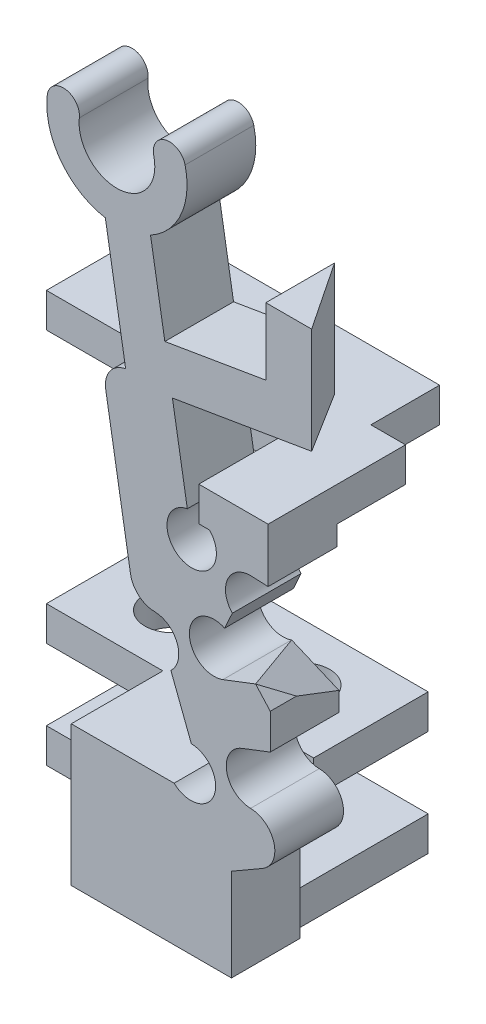
SolidWorks part; units mm, degrees
ref_plane "Front Plane" through (0, 0, 0) normal (0, 0, 1) x (1, 0, 0)
ref_plane "Top Plane" through (0, 0, 0) normal (0, 1, 0) x (1, 0, 0)
ref_plane "Right Plane" through (0, 0, 0) normal (1, 0, 0) x (0, 0, -1)
sketch "Sketch-SkeletonConfigUp" plane through (0, 0, 0) normal (0, 0, 1) x (1, 0, 0)
  line L0 (0, 0) -> (0, -50000) construction
  line L1 (0, 0) -> (4.5811, 6.2164) construction
  line L2 (9.8143, 13.3177) -> (4.5811, 13.945) construction
  line L3 (4.5811, 13.945) -> (2.9713, 10.4094) construction
  line L4 (2.9713, 10.4094) -> (4.5811, 6.2164) construction
  line L5 (4.5811, 13.945) -> (6.2429, 19.1409) construction
  line L6 (2.9713, 10.4094) -> (0.0405, 27.8193) construction
  line L7 (4.5811, 6.2164) -> (9.8143, 13.3177) construction
  line L8 (-587.3593, -797.0242) -> (9.8143, 13.3177) construction
  dimension "D2" = 7.7221
  dimension "D3" = 8.8212
  dimension "D4" = 5.2707
  dimension "D5" = 119.553
  dimension "D6" = 3.8848
  dimension "D7" = 5.4552
  dimension "D8" = 17.6549
  dimension "D9" = 4.4914
  dimension "D10" = 6.745
  dimension "D11" = 145.964
  dimension "D12" = 143.612
sketch "Sketch-SkeletonConfigDown" plane through (0, 0, 0) normal (0, 0, 1) x (1, 0, 0)
  line L0 (0, 0) -> (0, -50000) construction
  line L1 (0, 0) -> (4.5811, 6.2164) construction
  line L2 (9.8143, 13.3177) -> (4.5811, 13.945) construction
  line L3 (4.5811, 13.945) -> (6.1909, 10.4094) construction
  line L4 (6.1909, 10.4094) -> (4.5811, 6.2164) construction
  line L5 (4.5811, 13.945) -> (1.753, 18.6098) construction
  line L6 (6.1909, 10.4094) -> (-8.8652, 19.6294) construction
  line L7 (4.5811, 6.2164) -> (9.8143, 13.3177) construction
  line L8 (-589.9357, -800.5203) -> (9.8143, 13.3177) construction
  dimension "D2" = 7.7221
  dimension "D3" = 8.8212
  dimension "D4" = 5.2707
  dimension "D5" = 119.553
  dimension "D6" = 3.8848
  dimension "D7" = 5.4552
  dimension "D8" = 17.6549
  dimension "D9" = 4.4914
  dimension "D10" = 6.745
  dimension "D11" = 145.964
  dimension "D1" = 143.612
sketch "Sketch-SwitchBossUp" plane through (0, 0, 0) normal (0, 0, 1) x (1, 0, 0)
  line L0 (2.6478, 12.1123) -> (3.2566, 13.4492) construction
  line L1 (4.3447, 11.0125) -> (5.0768, 12.6205) construction
  line L2 (6.5405, 22.165) -> (6.5405, 25.0939)
  line L3 (6.5405, 25.0939) -> (8.5405, 25.0939)
  line L4 (8.5405, 25.0939) -> (8.5405, 20.4736)
  line L5 (4.5811, 13.945) -> (2.9713, 10.4094) construction
  line L7 (1.507, 25.1315) -> (2.1313, 21.4228)
  line L8 (-0.4652, 24.7995) -> (0.4213, 19.5329)
  line L9 (2.9713, 10.4094) -> (0.0405, 27.8193) construction
  line L10 (4.8917, 12.214) -> (3.0715, 13.0428) construction
  line L11 (-0.0396, 22.2712) -> (1.9326, 22.6032) construction
  line L13 (2.3961, 9.1174) -> (3.2891, 6.7916)
  line L14 (4.2633, 9.8343) -> (5.1563, 7.5084) construction
  line L15 (4.7098, 8.6713) -> (2.8426, 7.9545) construction
  line L16 (2.9713, 10.4094) -> (4.5811, 6.2164) construction
  line L17 (3.2566, 13.4492) -> (4.0854, 15.2694) construction
  line L18 (5.0768, 12.6205) -> (5.9056, 14.4407) construction
  line L19 (4.2853, 14.0796) -> (4.8769, 13.8103) construction
  line L20 (4.0854, 15.2694) -> (5.9056, 14.4407) construction
  line L21 (3.2566, 13.4492) -> (5.0768, 12.6205) construction
  line L22 (4.1667, 13.0349) -> (4.9955, 14.8551) construction
  line L23 (4.6678, 9.9058) -> (4.2913, 9.7612) construction
  line L24 (2.3961, 9.1174) -> (1.6793, 10.9845) construction
  line L25 (4.2633, 9.8343) -> (3.5464, 11.7014) construction
  line L26 (4.2633, 9.8343) -> (2.3961, 9.1174) construction
  line L27 (1.6793, 10.9845) -> (3.5464, 11.7014) construction
  line L28 (3.2891, 6.7916) -> (5.1563, 7.5084) construction
  line L29 (3.2891, 6.7916) -> (4.006, 4.9244) construction
  line L30 (5.1563, 7.5084) -> (5.8731, 5.6413) construction
  line L31 (4.006, 4.9244) -> (5.8731, 5.6413) construction
  line L32 (4.8845, 6.3329) -> (4.2777, 6.0999) construction
  line L36 (4.0854, 15.2694) -> (3.6136, 15.2694)
  line L40 (3.2747, 10.5259) -> (2.6679, 10.2929) construction
  line L43 (2.5363, 4.9244) -> (-1.9548, 4.9244)
  line L44 (-1.9548, 4.9244) -> (-1.9548, -1.1895)
  line L45 (-1.9548, -1.1895) -> (5.0405, -1.1895)
  line L46 (5.0405, -1.1895) -> (5.0405, 2.8478)
  line L51 (6.5405, 22.165) -> (2.1313, 21.4228)
  line L61 (6.6395, 14.4084) -> (6.6395, 16.7694)
  line L66 (0.0405, 27.8193) -> (0.0405, 50027.8193) construction
  line L73 (5.0768, 12.6205) -> (4.7428, 11.8869)
  line L74 (0.6325, 11.8929) -> (-0.448, 18.3116)
  line L75 (0.2173, 14.3595) -> (2.2273, 14.4682) construction
  line L76 (4.7428, 11.8869) -> (5.0768, 12.6205) construction
  line L77 (5.5047, 7.726) -> (5.1282, 7.5815) construction
  line L78 (4.6678, 9.9058) -> (6.094, 10.4534)
  line L79 (5.5047, 7.726) -> (6.4934, 8.1056)
  line L80 (6.094, 10.4534) -> (6.7341, 9.7424)
  line L81 (7.7675, 8.2601) -> (7.7675, -49991.7399) construction
  line L82 (2.1313, 21.4228) -> (3.1136, 15.5877) construction
  line L83 (3.1136, 15.5877) -> (2.4634, 19.4505)
  line L84 (2.4634, 19.4505) -> (8.5405, 20.4736)
  line L85 (6.9307, 9.5241) -> (7.7675, 8.5948) construction
  line L86 (6.4934, 8.1056) -> (6.7341, 8.198) construction
  line L88 (3.6136, 16.7694) -> (6.6395, 16.7694)
  line L90 (5.9056, 14.4407) -> (6.6395, 14.4084)
  line L92 (3.7762, 8.3129) -> (6.9307, 9.5241) construction
  line L93 (6.3942, 3.6294) -> (5.0405, 2.8478)
  line L94 (3.6136, 15.2694) -> (3.6136, 16.7694)
  line L95 (2.1313, 21.4228) -> (2.4634, 19.4505) construction
  line L96 (2.2974, 20.4367) -> (8.5405, 21.4876) construction
  line L97 (2.2974, 20.4367) -> (1.3112, 20.2707) construction
  line L98 (6.4934, 8.1056) -> (4.8199, 9.9642) construction
  line L99 (4.5811, 6.2164) -> (6.094, 10.4534) construction
  line L100 (4.5811, 6.2164) -> (8.5405, 8.3528) construction
  line L101 (4.5811, 6.2164) -> (6.9307, 9.5241) construction
  line L102 (4.5811, 6.2164) -> (8.5405, 7.1023) construction
  line L103 (8.5405, 20.4736) -> (8.5405, 8.3528) construction
  line L104 (6.9307, 9.5241) -> (7.7675, 8.5948) construction
  line L105 (6.7341, 8.198) -> (6.4934, 8.1056)
  line L106 (5.386, 8.3129) -> (8.5406, 7.1018) construction
  line L107 (6.1909, 10.4094) -> (4.5811, 6.2164) construction
  line L109 (6.9307, 8.2735) -> (7.7675, 8.5948) construction
  line L110 (7.7675, 8.5948) -> (6.9307, 8.2735) construction
  line L111 (6.7341, 9.7424) -> (6.7341, 8.198)
  line L112 (6.7341, 9.7424) -> (6.9307, 9.5241) construction
  line L113 (6.7341, 8.198) -> (6.9307, 8.2735) construction
  line L114 (6.9307, 8.2735) -> (6.7341, 8.198) construction
  arc A0 (1.507, 25.1315) -> (3.0168, 28.5383) centre (0.0405, 27.8193) ccw
  arc A1 (-0.4652, 24.7995) -> (-3.0011, 28.1713) centre (0.0405, 27.8193) cw
  arc A2 (-3.0011, 28.1713) -> (-1.6023, 28.0095) centre (-2.3017, 28.0904) cw
  arc A3 (3.0168, 28.5383) -> (1.648, 28.2077) centre (2.3324, 28.373) ccw
  arc A4 (-1.6023, 28.0095) -> (1.648, 28.2077) centre (0.0405, 27.8193) ccw
  arc A5 (3.2566, 13.4492) -> (4.0854, 15.2694) centre (3.304, 14.5264) ccw
  arc A6 (5.0768, 12.6205) -> (5.9056, 14.4407) centre (5.8582, 13.3635) cw
  arc A7 (2.3961, 9.1174) -> (1.6793, 10.9845) centre (1.6613, 9.9064) ccw
  arc A8 (3.5464, 11.7014) -> (4.2633, 9.8343) centre (4.2813, 10.9124) ccw
  arc A9 (3.2891, 6.7916) -> (4.006, 4.9244) centre (3.2711, 5.7135) cw
  arc A10 (5.1563, 7.5084) -> (5.8731, 5.6413) centre (5.8911, 6.7194) ccw
  arc A18 (1.6793, 10.9845) -> (0.6325, 11.8929) centre (1.6973, 12.0626) cw
  arc A19 (-0.448, 18.3116) -> (0.4213, 19.5329) centre (0.5973, 18.4876) cw
  arc A20 (3.2566, 13.4492) -> (3.1136, 15.5877) centre (3.304, 14.5264) cw
  arc A21 (4.006, 4.9244) -> (2.5363, 4.9244) centre (3.2711, 5.7135) cw
  arc A22 (5.8731, 5.6413) -> (6.3942, 3.6294) centre (5.8551, 4.5632) cw
  arc A24 (3.5464, 11.7014) -> (4.7428, 11.8869) centre (4.2813, 10.9124) cw
  arc A25 (4.2633, 9.8343) -> (4.6678, 9.9058) centre (4.2813, 10.9124) ccw
  arc A26 (5.1563, 7.5084) -> (5.5047, 7.726) centre (5.8911, 6.7194) cw
  arc A28 (6.3942, 3.6294) -> (5.2541, 3.668) centre (5.8551, 4.5632) cw construction
  point P44 (3.7762, 8.3129)
  point P53 (4.5811, 13.945)
  point P63 (2.9713, 10.4094)
  point P93 (0.9465, 22.4372)
  dimension "D1" = 2
  dimension "D2" = 2
  dimension "D3" = 2
  dimension "D4" = 2
  dimension "D5" = 2
  dimension "D6" = 0.65
  dimension "D7" = 2
  dimension "D8" = 42
  dimension "D9" = 0.5
  dimension "D10" = 5
  dimension "D11" = 8.5
  dimension "D12" = 120
  dimension "D13" = 1.5
  dimension "D14" = 10
  dimension "D16" = 42
  dimension "D17" = 42
extrude "Boss-SwitchMain" add sketch "Sketch-SwitchBossUp" along normal blind 3
sketch "Sketch1" plane through (0, 0, 0) normal (0, 0, -1) x (-1, 0, 0)
  line L0 (1.9548, 4.9244) -> (1.9548, -1.1895) construction
  line L1 (-4.628, -1.1895) -> (1.9548, -1.1895)
  line L2 (-4.628, -1.1895) -> (-4.628, 0.3105)
  line L3 (-4.628, 0.3105) -> (1.9548, 0.3105)
  line L4 (1.9548, -1.1895) -> (1.9548, 0.3105)
  line L5 (-3.6136, 16.7694) -> (-6.6395, 16.7694)
  line L6 (-2.5363, 4.9244) -> (1.9548, 4.9244)
  line L7 (-2.5363, 4.9244) -> (-2.5363, 3.4244)
  line L8 (-2.5363, 3.4244) -> (1.9548, 3.4244)
  line L9 (1.9548, 4.9244) -> (1.9548, 3.4244)
  line L10 (-6.6395, 16.7694) -> (-6.6395, 15.2694)
  line L11 (-6.6395, 14.4084) -> (-6.6395, 16.7694) construction
  line L12 (-6.6395, 15.2694) -> (-3.6136, 15.2694)
  line L13 (-5.128, -1.2624) -> (-5.128, 8.0214) construction
  line L14 (-3.6136, 15.2694) -> (-3.6136, 16.7694)
  line L18 (-3.6136, 16.7694) -> (-3.6136, 15.2694) construction
  line L19 (-5.128, -1.2624) -> (-5.128, 8.0214) construction
  dimension "D1" = 1.5
  dimension "D2" = 1.5
  dimension "D3" = 1.5
  dimension "D4" = 0.5
extrude "Boss-Flange Width" add sketch "Sketch1" along normal blind 6
ref_plane "Plane-Sta2Sit Groove" through (0.0405, 0, 0) normal (1, 0, 0) x (0, 0, -1)
ref_plane "Plane-Cam Face" through (-12.0395, 0, 0) normal (1, 0, 0) x (0, 0, -1)
ref_plane "Plane-FlangeTop" through (-7.0395, 0, 0) normal (1, 0, 0) x (0, 0, -1)
sketch "Sketch2" plane through (-7.0395, 0, 0) normal (1, 0, 0) x (0, 0, -1)
  line L0 (6, 15.2694) -> (-3, 15.2694) construction
  line L1 (6, 16.7694) -> (1, 16.7694)
  line L2 (6, 16.7694) -> (6, 15.2694)
  line L3 (6, 15.2694) -> (1, 15.2694)
  line L4 (1, 16.7694) -> (1, 15.2694)
  line L5 (6, 3.4244) -> (0, 3.4244) construction
  line L6 (6, 4.9244) -> (1, 4.9244)
  line L7 (6, 4.9244) -> (6, 3.4244)
  line L8 (6, 3.4244) -> (1, 3.4244)
  line L9 (1, 4.9244) -> (1, 3.4244)
  line L10 (-3, -1.1895) -> (6, -1.1895) construction
  line L11 (6, 0.3105) -> (1, 0.3105)
  line L12 (6, 0.3105) -> (6, -1.1895)
  line L13 (6, -1.1895) -> (1, -1.1895)
  line L14 (1, 0.3105) -> (1, -1.1895)
  line L15 (0, 10.4094) -> (0, 27.8193) construction
  dimension "D1" = 1
extrude "Boss-Flange Height" add sketch "Sketch2" along normal up to surface (11.6675 mm away)
sketch "Sketch-HolePositions" plane through (0, -1.1895, 0) normal (0, -1, 0) x (1, 0, 0)
  line L0 (-7.0395, -3.5) -> (4.628, -3.5) construction
  line L2 (4.628, -6) -> (4.628, 0) construction
  line L3 (-1.9548, -1) -> (-7.0395, -1) construction
  line L4 (-7.0395, -22.2167) -> (-7.0395, 22.2167) construction
  point P6 (-4.0395, -3.5)
  point P7 (1.628, -3.5)
  dimension "D1" = 3
  dimension "D2" = 3
  dimension "D3" = 2.5
sketch "Sketch6" plane through (0, -1.1895, 0) normal (0, -1, 0) x (-1, 0, 0)
  point P0 (4.0395, 3.5)
  point P3 (-1.628, 3.5)
hole_wizard "Tap Drill for M2x0.4 Tap1" positions "Sketch6" profile "Sketch5" hole size "M2x0.4" standard "ANSI Metric" end condition through all
sketch "Sketch5" plane through (-4.0395, -1.1895, -3.5) normal (1, 0, 0) x (0, 0, -1)
  line L0 (0, 0) -> (0, 30.2666)
  line L1 (0, 30.2666) -> (0.8, 30.2666)
  line L2 (0.8, 30.2666) -> (0.8, 0)
  line L5 (0.8, 0) -> (0, 0)
  line L11 (0, -6.35) -> (0, 107.95) construction
  dimension "Thru Hole Dia." = 1.6
  dimension "Thru Hole Depth" = 30.2666
sketch "Sketch9" plane through (0, -1.1895, 0) normal (0, -1, 0) x (1, 0, 0)
  point P0 (-4.0395, -3.5)
  point P3 (1.628, -3.5)
hole_wizard "M2 Clearance Hole2" positions "Sketch9" profile "Sketch8" hole size "M2" standard "ANSI Metric"
sketch "Sketch8" plane through (-4.0395, -1.1895, -3.5) normal (1, 0, 0) x (0, 0, -1)
  line L0 (0, 0) -> (0, 6.835)
  line L1 (0, 6.835) -> (1.2, 6.114)
  line L2 (1.2, 6.114) -> (1.2, 0)
  line L5 (1.2, 0) -> (0, 0)
  line L10 (0, 6.835) -> (-1.2, 6.114) construction
  line L11 (0, -6.35) -> (0, 107.95) construction
  dimension "Hole Dia." = 2.4
  dimension "Hole Depth" = 6.114
  dimension "Drill Angle" = 118
sketch "Sketch10" plane through (0, 16.7694, 0) normal (0, 1, 0) x (1, 0, 0)
  line L1 (6.6395, 6) -> (5.128, 6)
  line L2 (6.6395, 6) -> (6.6395, 3)
  line L3 (6.6395, 3) -> (5.128, 3)
  line L5 (4.628, 7) -> (4.628, 1) construction
  line L6 (3.6136, 1) -> (-7.0395, 1) construction
  line L7 (5.128, 6.25) -> (5.128, 1) construction
  line L8 (5.128, 6) -> (5.128, 3)
  dimension "D1" = 2
extrude "Cut-Flange Ramp Clearance" cut sketch "Sketch10" against normal up to next
sketch "Sketch-Measurements for Derailleur Ramps" plane through (0, 0, 0) normal (0, 0, 1) x (1, 0, 0)
  line L0 (2.4634, 19.4505) -> (2.1313, 21.4228)
  line L1 (2.2974, 20.4367) -> (1.3112, 20.2707)
  line L2 (2.9713, 10.4094) -> (0.0405, 27.8193) construction
  line L3 (1.3112, 20.2707) -> (-4.0257, 16.6658)
  line L4 (6.1909, 10.4094) -> (-8.8652, 19.6294) construction
  line L5 (1.3112, 20.2707) -> (2.6012, 12.6077)
  line L6 (2.6012, 12.6077) -> (-4.0257, 16.6658)
  line L7 (-1.3573, 18.4682) -> (-1.3573, 20.2707)
  line L8 (-1.3573, 20.2707) -> (1.3112, 20.2707)
  line L9 (6.1909, 10.4094) -> (2.9713, 10.4094)
  line L10 (5.386, 8.3129) -> (3.7762, 8.3129)
  line L12 (6.1909, 10.4094) -> (4.5811, 6.2164) construction
  line L13 (4.5811, 8.3129) -> (4.5811, 8.7912)
  line L14 (4.5811, 6.2164) -> (5.386, 8.3129)
  line L15 (2.9713, 10.4094) -> (4.5811, 6.2164) construction
  line L16 (3.7762, 8.3129) -> (4.5811, 6.2164)
  line L17 (5.386, 8.3129) -> (5.386, 8.7912)
  dimension "D1" = 2.6685
  dimension "D2" = 0.8049
sketch "Sketch12" plane through (0, 25.0939, 0) normal (0, 1, 0) x (1, 0, 0)
  line L0 (6.5405, 0) -> (8.5405, -3)
  line L1 (8.5405, -3) -> (8.5405, 0)
  line L2 (8.5405, 0) -> (6.5405, 0)
extrude "Cut-Extrude1" cut sketch "Sketch12" against normal up to next
ref_plane "Plane1" through (0, 7.1023, 0) normal (0, 1, 0) x (1, 0, 0)
sketch "Sketch-Derailleur Location" plane through (0, 7.1023, 0) normal (0, 1, 0) x (1, 0, 0)
  line L0 (8.5405, 0) -> (8.5405, -3)
  line L1 (2.2257, -3) -> (4.3822, -3) construction
  point P0 (8.5405, 0)
  point P8 (8.5405, -1.5)
ref_plane "Plane-Cantilever Cut" through (3.7891, 8.959, -3.4367) normal (-0.3673, -0.8684, 0.3331) x (-0.9301, 0.3429, -0.1315)
sketch "Sketch14" plane through (3.7891, 8.959, -3.4367) normal (-0.3673, -0.8684, 0.3331) x (-0.9301, 0.3429, -0.1315)
  line L0 (-0.9447, -3.5478) -> (-4.2773, -3.0783)
  line L2 (-1.432, -6.9644) -> (-0.9447, -3.5478)
  line L3 (-4.2773, -3.0783) -> (-4.8248, -6.9644)
  line L4 (-4.8248, -6.9644) -> (-1.432, -6.9644)
extrude "Cut-Extrude2" cut sketch "Sketch14" against normal up to next
equation "\"axle-diameter\"=2"
equation "\"switch-thickness\"=12"
equation "\"base-width\"=4.0"
equation "\"axle-bushing-radius\"=3"
equation "\"clearance\"= 0.25"
equation "\"arm-width\"=1.5"
equation "\"min-diameter\"=70"
equation "\"alpha\"=143.6120"
equation "\"gamma\"=119.5526"
equation "\"delta\"=145.9637"
equation "\"epsilon\"=6.7452"
equation "\"l_AB\"=8.8212"
equation "\"l_AC\"=4.4914"
equation "\"l_BD\"=5.2707"
equation "\"l_CD\"=3.8848"
equation "\"l_CE\"=17.6549"
equation "\"l_DF\"=5.4552"
equation "\"l_OA\"=7.7221"
equation "\"D2@Sketch-SkeletonConfigUp\" = \"l_OA\""
equation "\"D3@Sketch-SkeletonConfigUp\" = \"l_AB\""
equation "\"D4@Sketch-SkeletonConfigUp\" = \"l_BD\""
equation "\"D5@Sketch-SkeletonConfigUp\" = \"gamma\""
equation "\"D6@Sketch-SkeletonConfigUp\" = \"l_CD\""
equation "\"D7@Sketch-SkeletonConfigUp\" = \"l_DF\""
equation "\"D8@Sketch-SkeletonConfigUp\" = \"l_CE\""
equation "\"D9@Sketch-SkeletonConfigUp\" = \"l_AC\""
equation "\"D_groove\"=3.175"
equation "\"D7@Sketch-SkeletonConfigDown\" = \"l_DF\""
equation "\"D6@Sketch-SkeletonConfigDown\" = \"l_CD\""
equation "\"D2@Sketch-SkeletonConfigDown\" = \"l_OA\""
equation "\"D3@Sketch-SkeletonConfigDown\" = \"l_AB\""
equation "\"D9@Sketch-SkeletonConfigDown\" = \"l_AC\""
equation "\"D8@Sketch-SkeletonConfigDown\" = \"l_CE\""
equation "\"D5@Sketch-SkeletonConfigDown\" = \"gamma\""
equation "\"D4@Sketch-SkeletonConfigDown\" = \"l_BD\""
equation "\"D1@Sketch-SkeletonConfigDown\" = \"alpha\""
equation "\"hinge_length\"=1.5"
equation "\"hinge_depth\"=0.25"
equation "\"D10@Sketch-SkeletonConfigUp\"=\"epsilon\""
equation "\"D11@Sketch-SkeletonConfigUp\"=\"delta\""
equation "\"D12@Sketch-SkeletonConfigUp\"=\"alpha\""
equation "\"D11@Sketch-SkeletonConfigDown\"=\"delta\""
equation "\"D10@Sketch-SkeletonConfigDown\"=\"epsilon\""
equation "\"EE_dx\"=8.9056"
equation "\"EE_dy\"=8.1898"
equation "\"r_groove\"=\"D_groove\"/2"
equation "\"t_wall\"=25.4/16"
equation "\"width_lower\"=\"D_groove\"+\"t_wall\""
equation "\"cable_to_bottom\"=30.6257"
equation "\"switch_EE-up_base_dy\"=24"
equation "\"switch_EE-down_base_dy\"=16"
equation "\"D_axle\"=25.4/8"
equation "\"D_up_to_down\"=16"
equation "\"D_down_to_up\"=25"
equation "\"t_cam_base\"=7.5"
